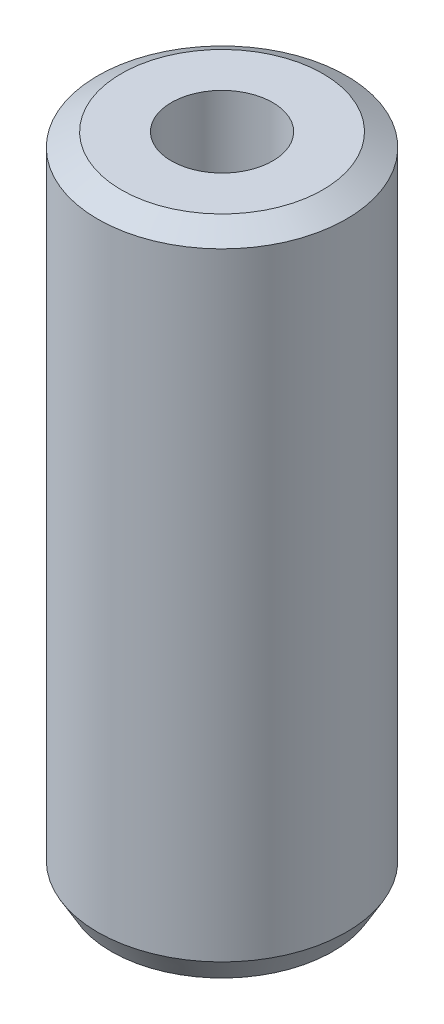
SolidWorks part; units mm, degrees
ref_plane "Front Plane" through (0, 0, 0) normal (0, 0, 1) x (1, 0, 0)
ref_plane "Top Plane" through (0, 0, 0) normal (0, 1, 0) x (1, 0, 0)
ref_plane "Right Plane" through (0, 0, 0) normal (1, 0, 0) x (0, 0, -1)
sketch "Sketch1" plane through (0, 0, 0) normal (0, 1, 0) x (1, 0, 0)
  circle A0 centre (0, 0) radius 35
  dimension "SHAFT_OD" = 70
extrude "Boss-Extrude1" add sketch "Sketch1" along normal blind 184.3575
sketch "Sketch2" plane through (0, 0, 0) normal (0, 1, 0) x (1, 0, 0)
  circle A0 centre (0, 0) radius 14.2677
  dimension "BORE_D" = 28.5355
extrude "Cut-Extrude1" cut sketch "Sketch2" along normal through all
chamfer "Chamfer1" distance 3.8269 angle 60 2 edges at (0, 184.3575, 35) (0, 0, 35) first distance on face at (0, 184.3575, 35) first distance on face at (0, 0, 14.2677)
